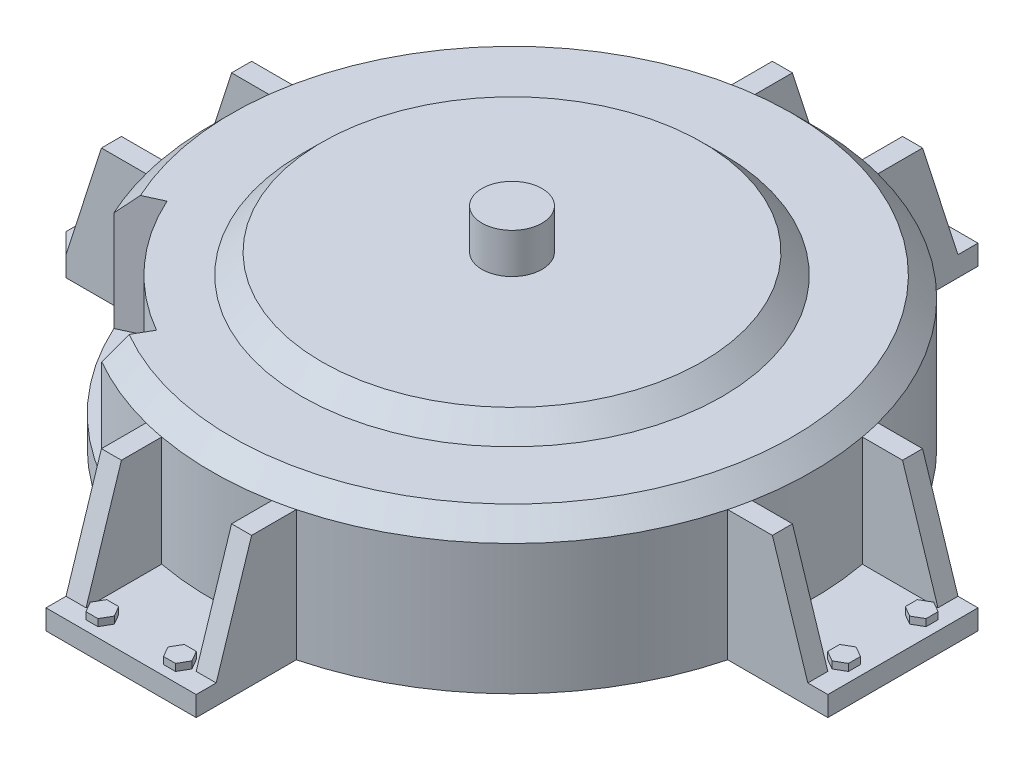
SolidWorks part; units mm, degrees
ref_plane "Front Plane" through (0, 0, 0) normal (0, 0, 1) x (1, 0, 0)
ref_plane "Top Plane" through (0, 0, 0) normal (0, 1, 0) x (1, 0, 0)
ref_plane "Right Plane" through (0, 0, 0) normal (1, 0, 0) x (0, 0, -1)
sketch "Sketch1" plane through (0, 0, 0) normal (0, 1, 0) x (1, 0, 0)
  circle A0 centre (0, 0) radius 150
  dimension "D1" = 300
extrude "Boss-Extrude1" add sketch "Sketch1" along normal blind 75
chamfer "Chamfer1" distance 10 angle 45 1 edges at (0, 75, 150)
sketch "Sketch2" plane through (0, 0, 0) normal (0, -1, 0) x (1, 0, 0)
  line L1 (-195.2369, 37.5) -> (-145.2369, 37.5)
  line L2 (-195.2369, 37.5) -> (-195.2369, -37.5)
  line L3 (-195.2369, -37.5) -> (-145.2369, -37.5)
  circle A0 centre (0, 0) radius 150 construction
  circle A1 centre (0, 0) radius 150
  point P0 (-150, 0)
  circle M6 centre (0, 0) radius 150
  dimension "D1" = 75
  dimension "D2" = 50
  dimension "D3" = 37.5
extrude "Boss-Extrude2" add sketch "Sketch2" against normal blind 10 contours L2 L3 L1 M6 region at (-171.8083, 0, 0)
chamfer "Chamfer2" distance 10 angle 45 2 edges at (-195.2369, 5, -37.5) (-195.2369, 5, 37.5)
sketch "Sketch3" plane through (0, 0, 37.5) normal (0, 0, 1) x (1, 0, 0)
  line L0 (-145.2369, 10) -> (-145.2369, 65)
  line L1 (-150, 65) -> (150, 65) construction
  line L2 (-145.2369, 65) -> (-167.5569, 65)
  line L3 (-167.5569, 65) -> (-185.2369, 10)
  line L4 (-185.2369, 10) -> (-145.2369, 10)
  line L5 (-185.2369, 10) -> (-185.2369, 0) construction
  line L6 (-185.2369, 10) -> (-145.2369, 10) construction
  dimension "D1" = 17.68
extrude "Boss-Extrude3" add sketch "Sketch3" against normal blind 10 contours L4 L0 L2 L3
sketch "Sketch4" plane through (0, 10, 0) normal (0, 1, 0) x (1, 0, 0)
  line L0 (-185.2369, 37.5) -> (-185.2369, -80.8824) construction
  line L2 (-185.2369, -13.385) -> (-190.433, -16.385)
  line L3 (-190.433, -16.385) -> (-190.433, -22.385)
  line L4 (-190.433, -22.385) -> (-185.2369, -25.385)
  line L5 (-185.2369, -25.385) -> (-180.0407, -22.385)
  line L6 (-180.0407, -22.385) -> (-180.0407, -16.385)
  line L7 (-180.0407, -16.385) -> (-185.2369, -13.385)
  circle A0 centre (-185.2369, -19.385) radius 5.1962 construction
  dimension "D1" = 6
extrude "Boss-Extrude4" add sketch "Sketch4" along normal blind 3.5
mirror "Mirror1" about plane through (0, 0, 0) normal (0, 0, 1) of "Boss-Extrude3", "Boss-Extrude4"
pattern_circular "CirPattern1" count 4 over 360 about axis through (0, 0, 0) along (0, 1, 0) of "Boss-Extrude2", "Boss-Extrude3", "Boss-Extrude4", "Mirror1"
sketch "Sketch5" plane through (0, 75, 0) normal (0, 1, 0) x (1, 0, 0)
  line L2 (-118.1912, -54.1371) -> (-136.3745, -62.4659)
  line L3 (-65, -112.5833) -> (-75, -129.9038)
  arc A1 (-118.1912, -54.1371) -> (-65, -112.5833) centre (0, 0) ccw
  arc A2 (-136.3745, -62.4659) -> (-75, -129.9038) centre (0, 0) ccw
extrude "Cut-Extrude1" cut sketch "Sketch5" against normal blind 60
sketch "Sketch6" plane through (0, 75, 0) normal (0, 1, 0) x (1, 0, 0)
  circle A0 centre (0, 0) radius 110
  dimension "D1" = 220
extrude "Boss-Extrude5" add sketch "Sketch6" along normal blind 10 contours A0
chamfer "Chamfer3" distance 15 angle 45 1 edges at (0, 85, 110)
sketch "Sketch7" plane through (0, 85, 0) normal (0, 1, 0) x (1, 0, 0)
  circle A0 centre (0, 0) radius 15
  dimension "D1" = 30
extrude "Boss-Extrude6" add sketch "Sketch7" along normal blind 20
